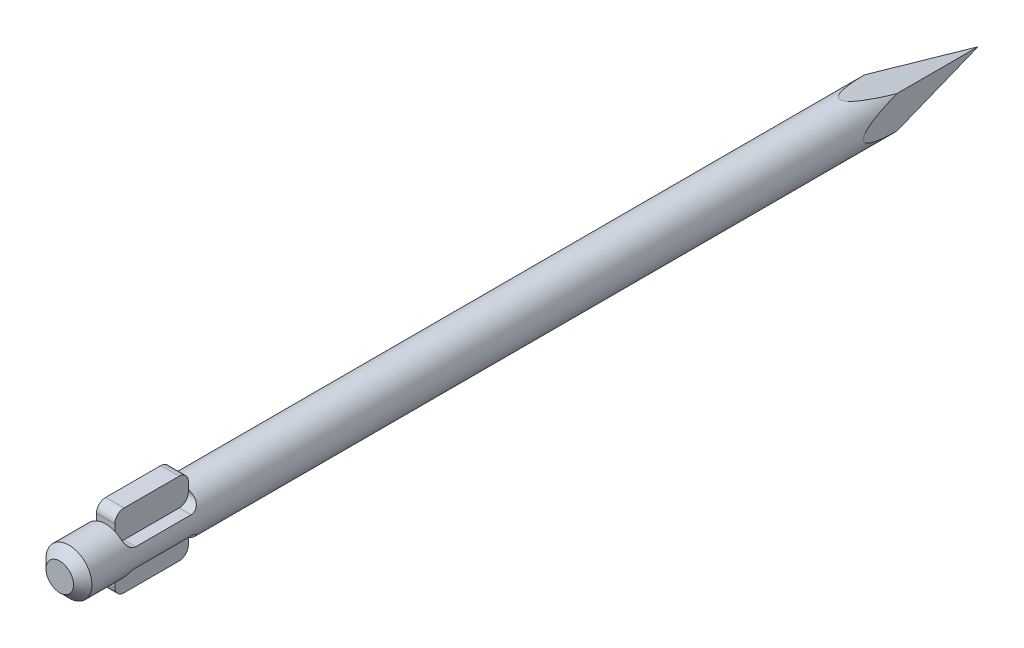
SolidWorks part; units mm, degrees
ref_plane "Front Plane" through (0, 0, 0) normal (0, 0, 1) x (1, 0, 0)
ref_plane "Top Plane" through (0, 0, 0) normal (0, 1, 0) x (1, 0, 0)
ref_plane "Right Plane" through (0, 0, 0) normal (1, 0, 0) x (0, 0, -1)
sketch "Sketch1" plane through (0, 0, 0) normal (0, 0, 1) x (1, 0, 0)
  circle A0 centre (0, 0) radius 2.5
  dimension "D1" = 5
extrude "Boss-Extrude1" add sketch "Sketch1" along normal blind 100
sketch "Sketch2" plane through (0, 0, 0) normal (1, 0, 0) x (0, 0, -1)
  line L0 (-100, 0) -> (-74.7701, 0) construction
  line L1 (-94, 4) -> (-88, 4)
  line L2 (-95, 3) -> (-95, 2)
  line L3 (-94, 1) -> (-88, 1)
  line L4 (-87, 3) -> (-87, 2)
  line L5 (-100, 2.5) -> (-100, -2.5) construction
  line L6 (-95, -3) -> (-95, -2)
  line L7 (-94, -1) -> (-88, -1)
  line L8 (-87, -3) -> (-87, -2)
  line L9 (-94, -4) -> (-88, -4)
  arc A0 (-94, 4) -> (-95, 3) centre (-94, 3) ccw
  arc A1 (-88, 4) -> (-87, 3) centre (-88, 3) cw
  arc A2 (-88, 1) -> (-87, 2) centre (-88, 2) ccw
  arc A3 (-95, 2) -> (-94, 1) centre (-94, 2) ccw
  arc A4 (-94, -4) -> (-95, -3) centre (-94, -3) cw
  arc A5 (-95, -2) -> (-94, -1) centre (-94, -2) cw
  arc A6 (-88, -1) -> (-87, -2) centre (-88, -2) cw
  arc A7 (-88, -4) -> (-87, -3) centre (-88, -3) ccw
  point P4 (-95, 2.5)
  point P13 (-95, 4)
  point P16 (-87, 4)
  point P19 (-87, 1)
  dimension "D5" = 1
  dimension "D1" = 8
  dimension "D2" = 3
  dimension "D3" = 5
  dimension "D4" = 1
extrude "Cut-Extrude1" cut sketch "Sketch2" against normal mid plane 5
extrude "Boss-Extrude2" add sketch "Sketch2<2>" along normal mid plane 2
sketch "Sketch2<2>" plane through (0, 0, 0) normal (1, 0, 0) x (0, 0, -1) same geometry as "Sketch2"
chamfer "Chamfer1" distance 1 angle 45 1 edges at (2.5, 0, 100)
sketch "Sketch3" plane through (0, 0, 0) normal (1, 0, 0) x (0, 0, -1)
  line L0 (0, 0) -> (-15, 2.5)
  line L1 (0, 2.5) -> (-87, 2.5) construction
  line L2 (0, 0) -> (-15, -2.5)
  line L3 (-87, -2.5) -> (0, -2.5) construction
  line L4 (-15, 2.5) -> (0, 2.5)
  line L5 (0, 2.5) -> (0, -2.5)
  line L6 (0, -2.5) -> (-15, -2.5)
  dimension "D1" = 15
  dimension "D2" = 15
extrude "Cut-Extrude2" cut sketch "Sketch3" against normal mid plane 5 contours L6 L5 L2 | L5 L4 L0 region at (0, -1.6667, 5) region at (0, 1.6667, 5)
sketch "Sketch4" plane through (0, 0, 0) normal (0, 1, 0) x (1, 0, 0)
  line L0 (0, 0) -> (-2.5, -15)
  line L1 (-2.5, 0) -> (-2.5, -99) construction
  line L2 (0, 0) -> (2.5, -15)
  line L3 (2.5, -99) -> (2.5, 0) construction
  line L4 (2.5, -15) -> (2.5, 0)
  line L5 (2.5, 0) -> (-2.5, 0)
  line L6 (-2.5, 0) -> (-2.5, -15)
  dimension "D1" = 15
  dimension "D2" = 15
extrude "Cut-Extrude3" cut sketch "Sketch4" against normal mid plane 5 contours L5 L6 L0 | L4 L5 L2 region at (1.6667, 0, 5) region at (-1.6667, 0, 5)
